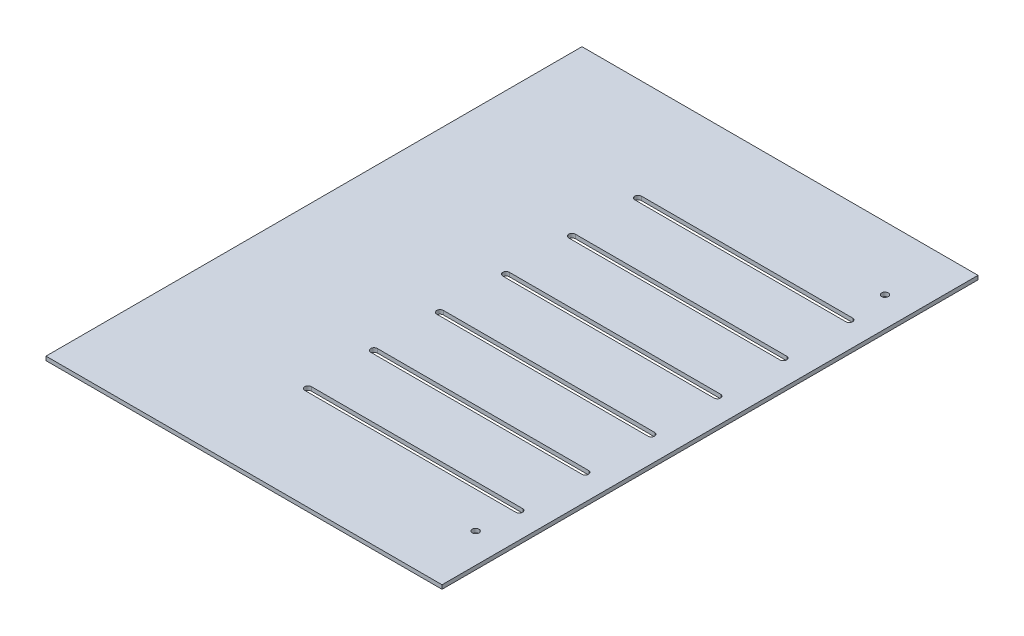
SolidWorks part; units mm, degrees
ref_plane "Front Plane" through (0, 0, 0) normal (0, 0, 1) x (1, 0, 0)
ref_plane "Top Plane" through (0, 0, 0) normal (0, 1, 0) x (1, 0, 0)
ref_plane "Right Plane" through (0, 0, 0) normal (1, 0, 0) x (0, 0, -1)
sketch "Sketch1" plane through (0, 0, 0) normal (0, 1, 0) x (1, 0, 0)
  line L1 (-150, -203) -> (150, -203)
  line L2 (-150, -203) -> (-150, 203)
  line L3 (-150, 203) -> (150, 203)
  line L4 (150, -203) -> (150, 203)
  line L5 (-150, -203) -> (150, 203) construction
  line L6 (-150, 203) -> (150, -203) construction
  point P0 (0, 0)
  dimension "D1" = 406
  dimension "D2" = 300
extrude "Boss-Extrude1" add sketch "Sketch1" along normal blind 3
sketch "Sketch2" plane through (0, 3, 0) normal (0, 1, 0) x (1, 0, 0)
  line L0 (0, -1000) -> (0, 49000) construction
  line L1 (115, -1000) -> (115, 49000) construction
  line L2 (150, -203) -> (150, 203) construction
  line L3 (150, 203) -> (-150, 203) construction
  line L6 (115, 125) -> (-14, 125) construction
  circle A0 centre (115, 125) radius 2.5
  circle A1 centre (115, 75) radius 2.5
  circle A2 centre (115, 25) radius 2.5
  circle A3 centre (115, -25) radius 2.5
  circle A4 centre (115, -75) radius 2.5
  circle A5 centre (115, -125) radius 2.5
  circle A12 centre (-14, 125) radius 2.5
  circle A13 centre (-14, 75) radius 2.5
  circle A14 centre (-14, 25) radius 2.5
  circle A15 centre (-14, -25) radius 2.5
  circle A16 centre (-14, -75) radius 2.5
  circle A17 centre (-14, -125) radius 2.5
  dimension "D2" = 78
  dimension "D3" = 5
  dimension "D5" = 50
  dimension "D6" = 2
  dimension "D1" = 35
  dimension "D7" = 129
  dimension "D4" = 6
extrude "Cut-Extrude1" cut sketch "Sketch2" against normal up to next
sketch "Sketch3" plane through (0, 3, 0) normal (0, 1, 0) x (1, 0, 0)
  line L0 (-1000, 0) -> (49000, 0) construction
  line L1 (-150, -203) -> (150, -203) construction
  line L2 (150, -203) -> (150, 203) construction
  circle A0 centre (127.5, -155) radius 2.5
  circle A1 centre (127.5, 155) radius 2.5
  dimension "D2" = 5
  dimension "D1" = 48
  dimension "D3" = 22.5
extrude "Cut-Extrude2" cut sketch "Sketch3" against normal through all
sketch "Sketch4" plane through (0, 3, 0) normal (0, 1, 0) x (1, 0, 0)
  line L0 (-1000, 0) -> (49000, 0) construction
  line L1 (130.5, -25) -> (-29.5, -25) construction
  line L2 (130.5, -27.5) -> (-29.5, -27.5)
  line L3 (130.5, -22.5) -> (-29.5, -22.5)
  line L4 (50.5, -1025) -> (50.5, 48975) construction
  line L5 (150, -203) -> (150, 203) construction
  line L6 (130.5, -75) -> (-29.5, -75) construction
  line L7 (130.5, -77.5) -> (-29.5, -77.5)
  line L8 (130.5, -72.5) -> (-29.5, -72.5)
  line L9 (130.5, -125) -> (-29.5, -125) construction
  line L10 (130.5, -127.5) -> (-29.5, -127.5)
  line L11 (130.5, -122.5) -> (-29.5, -122.5)
  line L12 (130.5, -25) -> (130.5, -75) construction
  line L13 (130.5, 25) -> (-29.5, 25) construction
  line L14 (130.5, 27.5) -> (-29.5, 27.5)
  line L15 (130.5, 22.5) -> (-29.5, 22.5)
  line L16 (130.5, 75) -> (-29.5, 75) construction
  line L17 (130.5, 77.5) -> (-29.5, 77.5)
  line L18 (130.5, 72.5) -> (-29.5, 72.5)
  line L19 (130.5, 125) -> (-29.5, 125) construction
  line L20 (130.5, 127.5) -> (-29.5, 127.5)
  line L21 (130.5, 122.5) -> (-29.5, 122.5)
  arc A0 (130.5, -27.5) -> (130.5, -22.5) centre (130.5, -25) ccw
  arc A1 (-29.5, -22.5) -> (-29.5, -27.5) centre (-29.5, -25) ccw
  circle A2 centre (-14, -25) radius 2.5 construction
  arc A3 (130.5, -77.5) -> (130.5, -72.5) centre (130.5, -75) ccw
  arc A4 (-29.5, -72.5) -> (-29.5, -77.5) centre (-29.5, -75) ccw
  arc A5 (130.5, -127.5) -> (130.5, -122.5) centre (130.5, -125) ccw
  arc A6 (-29.5, -122.5) -> (-29.5, -127.5) centre (-29.5, -125) ccw
  arc A7 (130.5, 27.5) -> (130.5, 22.5) centre (130.5, 25) cw
  arc A8 (-29.5, 22.5) -> (-29.5, 27.5) centre (-29.5, 25) cw
  arc A9 (130.5, 77.5) -> (130.5, 72.5) centre (130.5, 75) cw
  arc A10 (-29.5, 72.5) -> (-29.5, 77.5) centre (-29.5, 75) cw
  arc A11 (130.5, 127.5) -> (130.5, 122.5) centre (130.5, 125) cw
  arc A12 (-29.5, 122.5) -> (-29.5, 127.5) centre (-29.5, 125) cw
  point P7 (50.5, -25)
  point P19 (50.5, -75)
  point P22 (115, -25)
  point P28 (50.5, -125)
  point P36 (50.5, 25)
  point P43 (50.5, 75)
  point P50 (50.5, 125)
  dimension "D1" = 99.5
  dimension "D2" = 160
  dimension "D4" = 50
  dimension "D3" = 3
extrude "Cut-Extrude3" cut sketch "Sketch4" against normal through all
